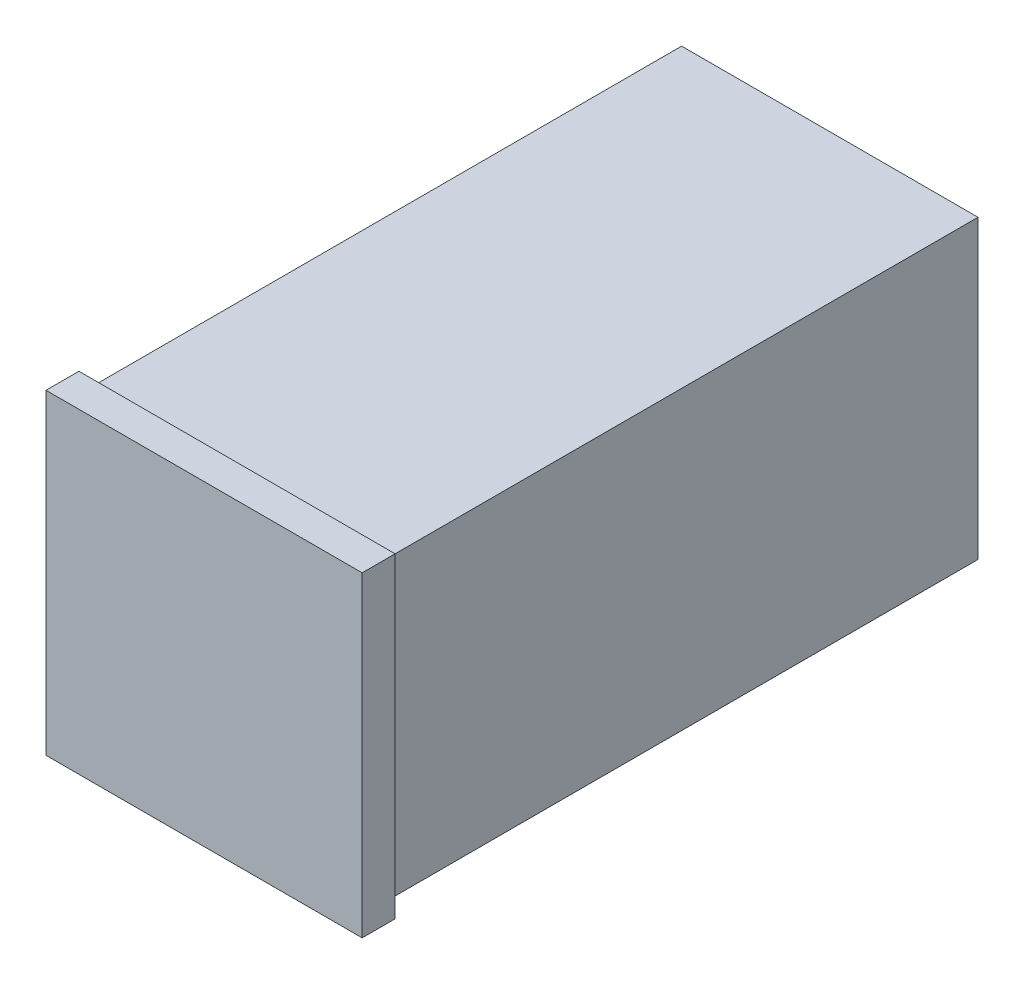
SolidWorks part; units mm, degrees
ref_plane "Front Plane" through (0, 0, 0) normal (0, 0, 1) x (1, 0, 0)
ref_plane "Top Plane" through (0, 0, 0) normal (0, 1, 0) x (1, 0, 0)
ref_plane "Right Plane" through (0, 0, 0) normal (1, 0, 0) x (0, 0, -1)
sketch "Sketch1" plane through (0, 0, 0) normal (0, 0, 1) x (1, 0, 0)
  line L0 (-1.5, 46.5) -> (46.5, 46.5)
  line L1 (0, 0) -> (45, 0)
  line L2 (0, 0) -> (0, 45)
  line L3 (0, 45) -> (45, 45)
  line L4 (45, 0) -> (45, 45)
  line L5 (46.5, -1.5) -> (46.5, 46.5)
  line L6 (-1.5, -1.5) -> (46.5, -1.5)
  line L7 (-1.5, -1.5) -> (-1.5, 46.5)
  dimension "D1" = 45
  dimension "D2" = 45
  dimension "D3" = 1.5
extrude "Boss-Extrude1" add sketch "Sketch1" along normal blind 5 contours L1 L4 L3 L2 | L7 L6 L5 L0 L4 L1 L2 L3 region at (22.5, 45.8212, 0) region at (22.5, 22.5, 0)
extrude "Boss-Extrude2" add sketch "Sketch1<2>" against normal blind 90 separate body contours L1 L4 L3 L2 region at (22.5, 22.5, 0)
sketch "Sketch1<2>" plane through (0, 0, 0) normal (0, 0, 1) x (1, 0, 0) same geometry as "Sketch1"
